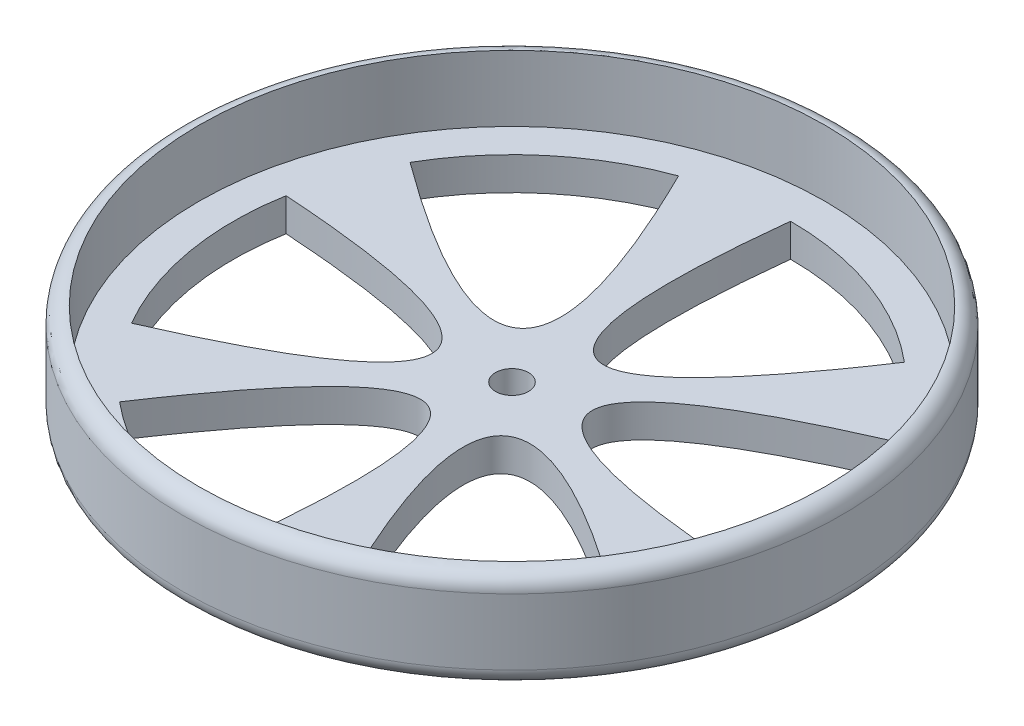
SolidWorks part; units mm, degrees
ref_plane "Front Plane" through (0, 0, 0) normal (0, 0, 1) x (1, 0, 0)
ref_plane "Top Plane" through (0, 0, 0) normal (0, 1, 0) x (1, 0, 0)
ref_plane "Right Plane" through (0, 0, 0) normal (1, 0, 0) x (0, 0, -1)
sketch "Sketch1" plane through (0, 0, 0) normal (0, 1, 0) x (1, 0, 0)
  circle A0 centre (0, 0) radius 25.4
  circle A2 centre (0, 0) radius 1.27
  circle A3 centre (0, 0) radius 21.4669
  circle A4 centre (0, 0) radius 5.0931
  spline S0 degree 2 poles (0, 21.4669) (-3.4155, -9.3839) (13.7987, 16.4446) knots 0 0 0 1 1 1
  spline S1 degree 2 poles (18.5909, 10.7335) (-9.8344, -1.7341) (21.1408, -3.7277) knots 0 0 0 1 1 1
  spline S2 degree 2 poles (18.5909, -10.7335) (-6.419, 7.6498) (7.3421, -20.1723) knots 0 0 0 1 1 1
  spline S3 degree 2 poles (0, -21.4669) (3.4155, 9.3839) (-13.7987, -16.4446) knots 0 0 0 1 1 1
  spline S4 degree 2 poles (-18.5909, -10.7335) (9.8344, 1.7341) (-21.1408, 3.7277) knots 0 0 0 1 1 1
  spline S5 degree 2 poles (-18.5909, 10.7335) (6.419, -7.6498) (-7.3421, 20.1723) knots 0 0 0 1 1 1
  point P8 (1.7419, 4.7859)
  point P26 (0, 0)
  point P28 (5.0157, 0.8844)
  point P29 (13.7987, 16.4446)
  point P32 (18.5909, -10.7335)
  point P34 (18.5909, 10.7335)
  point P35 (21.1408, -3.7277)
  point P38 (0, -21.4669)
  point P40 (3.2738, -3.9015)
  point P41 (7.3421, -20.1723)
  point P44 (-18.5909, -10.7335)
  point P46 (-13.7987, -16.4446)
  point P47 (-21.1408, -3.7277)
  point P48 (-18.5909, 10.7335)
  point P49 (-7.3421, 20.1723)
  point P50 (-1.7419, -4.7859)
  point P55 (-3.2738, 3.9015)
  point P57 (-21.1408, 3.7277)
  point P58 (-5.0157, -0.8844)
extrude "Boss-Extrude2" add sketch "Sketch1" along normal blind 7.62 contours A0
extrude "Cut-Extrude2" cut sketch "Sketch1<4>" along normal blind 47.498 contours A3 S5 | A3 S0 | A3 S1 | A3 S2 | A3 S3 | A3 S4 region at (14.4388, 0, -2.5459) region at (5.0145, 0, -13.7773) region at (9.4243, 0, 11.2314) region at (-9.4243, 0, -11.2314) region at (-5.0145, 0, 13.7773) region at (-14.4388, 0, 2.5459)
sketch "Sketch1<4>" plane through (0, 0, 0) normal (0, 1, 0) x (1, 0, 0) same geometry as "Sketch1"
extrude "Cut-Extrude5" cut sketch "Sketch1<5>" along normal blind 61.214 contours A2
sketch "Sketch1<5>" plane through (0, 0, 0) normal (0, 1, 0) x (1, 0, 0) same geometry as "Sketch1"
fillet "Fillet3" radius 1.27 1 edges at (0, 0, 25.4)
fillet "Fillet4" radius 1.27 1 edges at (0, 7.62, 25.4)
sketch "Sketch9" plane through (0, 7.62, 0) normal (0, 1, 0) x (1, 0, 0)
  circle A0 centre (0, 0) radius 24.13
extrude "Cut-Extrude7" cut sketch "Sketch9" against normal blind 5.08 contours A0
